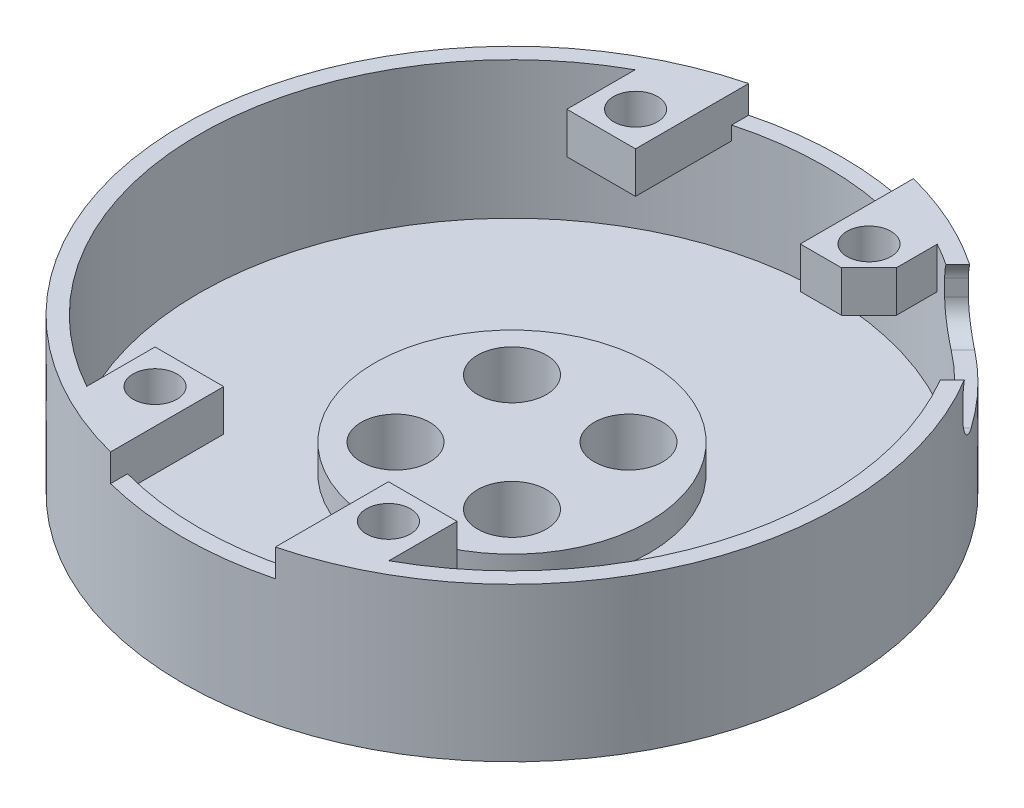
SolidWorks part; units mm, degrees
ref_plane "Front Plane" through (0, 0, 0) normal (0, 0, 1) x (1, 0, 0)
ref_plane "Top Plane" through (0, 0, 0) normal (0, 1, 0) x (1, 0, 0)
ref_plane "Right Plane" through (0, 0, 0) normal (1, 0, 0) x (0, 0, -1)
sketch "Sketch1" plane through (0, 0, 0) normal (0, 1, 0) x (1, 0, 0)
  line L0 (-4.2426, 4.2426) -> (4.2426, 4.2426) construction
  line L1 (4.2426, 4.2426) -> (4.2426, -4.2426) construction
  line L2 (4.2426, -4.2426) -> (-4.2426, -4.2426) construction
  line L3 (-4.2426, -4.2426) -> (-4.2426, 4.2426) construction
  circle A0 centre (0, 0) radius 9
  circle A1 centre (4.2426, 4.2426) radius 1.2
  circle A2 centre (-4.2426, 4.2426) radius 1.2
  circle A4 centre (4.2426, -4.2426) radius 1.2
  circle A5 centre (-4.2426, -4.2426) radius 1.2
  circle A6 centre (0, 0) radius 6 construction
  dimension "D1" = 18
  dimension "D6" = 2.4
  dimension "D7" = 2.4
  dimension "D8" = 2.4
  dimension "D9" = 2.4
  dimension "D2" = 12
extrude "Boss-Extrude1" add sketch "Sketch1" along normal blind 5
sketch "Sketch2" plane through (0, 5, 0) normal (0, 1, 0) x (1, 0, 0)
  circle A0 centre (0, 0) radius 24
  dimension "D1" = 48
extrude "Boss-Extrude2" add sketch "Sketch2" along normal blind 1.2
sketch "Sketch4" plane through (0, 5, 0) normal (0, -1, 0) x (1, 0, 0)
  circle A0 centre (-4.2426, -4.2426) radius 1.2 construction
  circle A1 centre (4.2426, -4.2426) radius 1.2 construction
  circle A2 centre (4.2426, 4.2426) radius 1.2 construction
  circle A3 centre (-4.2426, 4.2426) radius 1.2 construction
  circle A4 centre (-4.2426, -4.2426) radius 1.2
  circle A5 centre (4.2426, -4.2426) radius 1.2
  circle A6 centre (4.2426, 4.2426) radius 1.2
  circle A7 centre (-4.2426, 4.2426) radius 1.2
extrude "Cut-Extrude1" cut sketch "Sketch4" against normal through all
sketch "Sketch5" plane through (0, 6.2, 0) normal (0, 1, 0) x (1, 0, 0)
  circle A1 centre (0, 0) radius 10
  circle A2 centre (4.2426, -4.2426) radius 1.2 construction
  circle A3 centre (-4.2426, -4.2426) radius 1.2 construction
  circle A4 centre (-4.2426, 4.2426) radius 1.2 construction
  circle A5 centre (4.2426, 4.2426) radius 1.2 construction
  circle A6 centre (4.2426, -4.2426) radius 1.2
  circle A7 centre (-4.2426, -4.2426) radius 1.2
  circle A8 centre (-4.2426, 4.2426) radius 1.2
  circle A9 centre (4.2426, 4.2426) radius 1.2
  dimension "D1" = 20
extrude "Boss-Extrude4" add sketch "Sketch5" along normal blind 2
sketch "Sketch6" plane through (0, 6.2, 0) normal (0, 1, 0) x (1, 0, 0)
  circle A0 centre (0, 0) radius 22.8
  circle A1 centre (0, 0) radius 24 construction
  circle A2 centre (0, 0) radius 24
  dimension "D1" = 45.6
extrude "Boss-Extrude5" add sketch "Sketch6" along normal blind 10
sketch "Sketch7" plane through (0, 16.2, 0) normal (0, 1, 0) x (1, 0, 0)
  line L1 (6, -24) -> (-6, -24)
  line L2 (6, -24) -> (6, 24)
  line L3 (6, 24) -> (-6, 24)
  line L4 (-6, -24) -> (-6, 24)
  dimension "D1" = 12
  dimension "D2" = 48
  dimension "D3" = 6
  dimension "D4" = 24
extrude "Cut-Extrude2" cut sketch "Sketch7" against normal blind 2
sketch "Sketch9" plane through (0, 16.2, 0) normal (0, 1, 0) x (1, 0, 0)
  line L0 (-6, 21.9964) -> (-6, 14.9964)
  line L1 (-6, 14.9964) -> (-11, 14.9964)
  line L2 (-11, 14.9964) -> (-11, 19.971)
  line L3 (6, 21.9964) -> (6, 14.9964)
  line L4 (6, 14.9964) -> (11, 14.9964)
  line L5 (11, 14.9964) -> (11, 19.971)
  line L6 (-6, -21.9964) -> (-6, -14.9964)
  line L7 (-6, -14.9964) -> (-11, -14.9964)
  line L8 (-11, -14.9964) -> (-11, -19.971)
  line L9 (6, -21.9964) -> (6, -14.9964)
  line L10 (6, -14.9964) -> (11, -14.9964)
  line L11 (11, -14.9964) -> (11, -19.971)
  circle A0 centre (0, 0) radius 22.8 construction
  circle A1 centre (0, 0) radius 22.8
  circle A2 centre (-8.5, 17.5) radius 1.6
  circle A3 centre (8.5, 17.5) radius 1.6
  circle A4 centre (8.5, -17.5) radius 1.6
  circle A5 centre (-8.5, -17.5) radius 1.6
  arc M18 (-6, -21.9964) -> (-6, 21.9964) centre (0, 0) cw
  dimension "D1" = 3.2
  dimension "D2" = 3.2
  dimension "D3" = 3.2
  dimension "D4" = 3.2
  dimension "D5" = 35
  dimension "D6" = 17
  dimension "D7" = 8.5
  dimension "D8" = 17.5
  dimension "D9" = 7
  dimension "D10" = 5
  dimension "D11" = 7
  dimension "D12" = 5
  dimension "D13" = 7
  dimension "D14" = 5
  dimension "D15" = 7
  dimension "D16" = 5
extrude "Boss-Extrude6" add sketch "Sketch9" against normal blind 3 contours L7 L8 L6 A5 M18 | L9 A1 L11 L10 A4 | L5 A1 L3 L4 A3 | L2 L1 L0 A2 M18 region at (-6.086, 16.2, -18.4964) region at (8.5278, 16.2, -21.0523) region at (-10.914, 16.2, 17.4837) region at (8.5278, 16.2, 21.0523)
sketch "Sketch10" plane through (0, 8.2, 0) normal (0, 1, 0) x (1, 0, 0)
  circle A0 centre (4.2426, 4.2426) radius 2.5
  circle A1 centre (4.2426, -4.2426) radius 2.5
  circle A2 centre (-4.2426, -4.2426) radius 2.5
  circle A3 centre (-4.2426, 4.2426) radius 2.5
  dimension "D1" = 5
  dimension "D2" = 5
  dimension "D3" = 5
  dimension "D4" = 5
extrude "Cut-Extrude3" cut sketch "Sketch10" against normal blind 7
extrude "Boss-Extrude7" add sketch "Sketch1<2>" against normal blind 1
sketch "Sketch1<2>" plane through (0, 0, 0) normal (0, 1, 0) x (1, 0, 0) same geometry as "Sketch1"
ref_plane "Plane1" through (18.3211, 0, -18.3211) normal (0.7071, 0, -0.7071) x (-0.7071, 0, -0.7071)
sketch "Sketch15" plane through (18.3211, 0, -18.3211) normal (0.7071, 0, -0.7071) x (-0.7071, 0, -0.7071)
  line L8 (-4.092, 11.98) -> (2.848, 11.98)
  line L9 (4.818, 13.95) -> (4.818, 15.15)
  line L10 (2.848, 17.12) -> (-4.092, 17.12)
  line L11 (-6.062, 15.15) -> (-6.062, 13.95)
  line L12 (-4.092, 11.98) -> (2.848, 11.98)
  line L13 (4.818, 13.95) -> (4.818, 15.15)
  line L14 (2.848, 17.12) -> (-4.092, 17.12)
  line L15 (-6.062, 15.15) -> (-6.062, 13.95)
  arc A8 (-6.062, 13.95) -> (-4.092, 11.98) centre (-4.092, 13.95) ccw
  arc A9 (2.848, 11.98) -> (4.818, 13.95) centre (2.848, 13.95) ccw
  arc A10 (4.818, 15.15) -> (2.848, 17.12) centre (2.848, 15.15) ccw
  arc A11 (-4.092, 17.12) -> (-6.062, 15.15) centre (-4.092, 15.15) ccw
  arc A12 (-6.062, 13.95) -> (-4.092, 11.98) centre (-4.092, 13.95) ccw
  arc A13 (2.848, 11.98) -> (4.818, 13.95) centre (2.848, 13.95) ccw
  arc A14 (4.818, 15.15) -> (2.848, 17.12) centre (2.848, 15.15) ccw
  arc A15 (-4.092, 17.12) -> (-6.062, 15.15) centre (-4.092, 15.15) ccw
  dimension "D1" = 1
extrude "Cut-Extrude4" cut sketch "Sketch15" against normal blind 5
sketch "Sketch18" plane through (0, 16.2, 0) normal (0, 1, 0) x (1, 0, 0)
  line L0 (11, 14.9964) -> (11, 19.971) construction
  line L1 (11, 16.9964) -> (9, 14.9964)
  line L2 (6, 14.9964) -> (11, 14.9964) construction
  line L3 (9, 14.9964) -> (11, 14.9964)
  line L4 (11, 14.9964) -> (11, 16.9964)
  circle A0 centre (0, 0) radius 24
  circle A1 centre (0, 0) radius 24
  dimension "D1" = 2
  dimension "D2" = 2
extrude "Cut-Extrude5" cut sketch "Sketch18" against normal blind 5 flip side to cut
